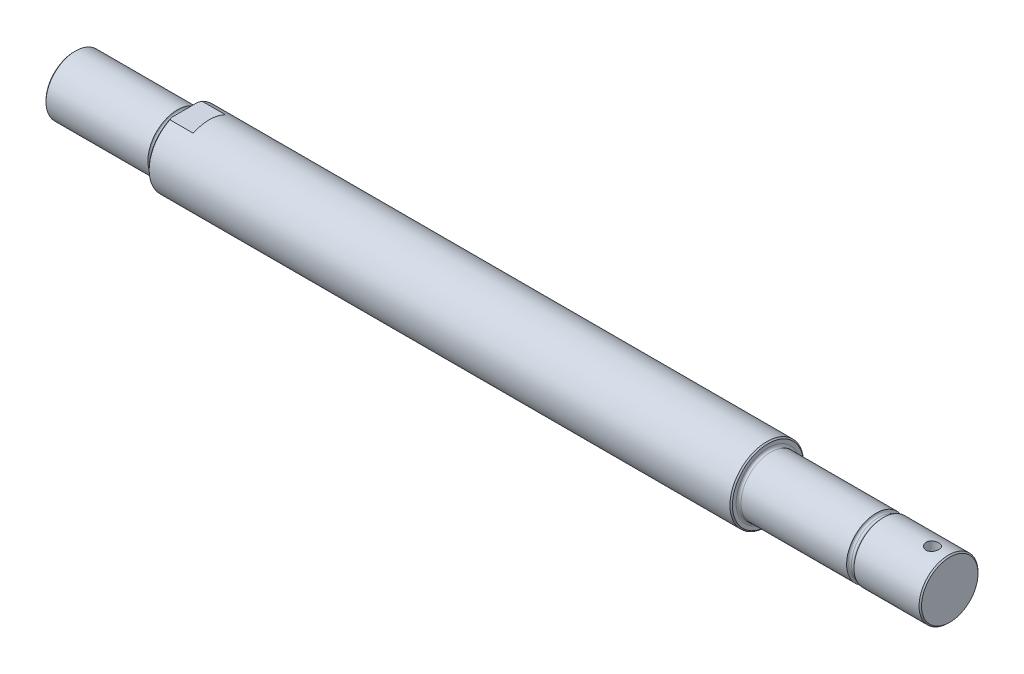
SolidWorks part; units mm, degrees
ref_plane "Front" through (0, 0, 0) normal (0, 0, 1) x (1, 0, 0)
ref_plane "Top" through (0, 0, 0) normal (0, 1, 0) x (1, 0, 0)
ref_plane "Right" through (0, 0, 0) normal (1, 0, 0) x (0, 0, -1)
ref_axis "Axis1" through (-84.4107, 0, 0) along (1, 0, 0)
ref_axis "Axis2" through (0, 64.3378, 0) along (0, -1, 0)
ref_axis "Axis3" through (0, 0, -102.329) along (0, 0, 1)
sketch "Sketch1" plane through (0, 0, 0) normal (0, 0, 1) x (1, 0, 0)
  line L0 (-178.25, 0) -> (178.25, 0) construction
  line L1 (-178.25, 15) -> (178.25, 15)
  line L2 (-178.25, 15) -> (-178.25, 0)
  line L3 (-178.25, 0) -> (178.25, 0)
  line L4 (178.25, 15) -> (178.25, 0)
  point P4 (0, 0)
  dimension "D1" = 15
  dimension "D2" = 356.5
revolve "Revolve1" add sketch "Sketch1" angle 360 about L0
sketch "Sketch2" plane through (0, 0, 0) normal (0, 0, 1) x (1, 0, 0)
  line L0 (178.25, 0) -> (-178.25, 0) construction
  line L1 (178.25, 15) -> (104.25, 15)
  line L2 (178.25, 15) -> (178.25, 12)
  line L3 (178.25, 12) -> (104.25, 12)
  line L4 (104.25, 15) -> (104.25, 12)
  line L5 (-178.25, 15) -> (-133.25, 15)
  line L6 (-178.25, 15) -> (-178.25, 12)
  line L7 (-178.25, 12) -> (-133.25, 12)
  line L8 (-133.25, 15) -> (-133.25, 12)
  line L9 (178.25, -15) -> (178.25, 15) construction
  line L10 (-178.25, 15) -> (-178.25, -15) construction
  line L11 (178.25, 12) -> (151.25, 12)
  line L13 (151.25, 12) -> (148.25, 12)
  line L14 (151.25, 12) -> (151.25, 11)
  line L15 (151.25, 11) -> (148.25, 11)
  line L16 (148.25, 12) -> (148.25, 11)
  line L17 (-133.25, 12) -> (-136.25, 12)
  line L18 (-133.25, 12) -> (-133.25, 11)
  line L19 (-133.25, 11) -> (-136.25, 11)
  line L20 (-136.25, 12) -> (-136.25, 11)
  dimension "D1" = 3
  dimension "D2" = 74
  dimension "D3" = 45
  dimension "D4" = 3
  dimension "D5" = 1
  dimension "D6" = 3
  dimension "D7" = 3
  dimension "D8" = 1
revolve "Cut-Revolve1" cut sketch "Sketch2" angle 360 about L0
sketch "Sketch3" plane through (0, 0, 0) normal (0, 1, 0) x (1, 0, 0)
  line L0 (178.25, 0) -> (171.25, 0)
  line L1 (178.25, -12) -> (178.25, 12) construction
  circle A0 centre (171.25, 0) radius 2.6
  dimension "D2" = 5.2
  dimension "D1" = 7
extrude "Cut-Extrude1" cut sketch "Sketch3" against normal through all both and the other way through all contours A0
sketch "Sketch4" plane through (0, 0, 0) normal (0, 0, 1) x (1, 0, 0)
  line L1 (-133.25, 15) -> (-123.25, 15)
  line L2 (-133.25, 15) -> (-133.25, 13.5)
  line L3 (-133.25, 13.5) -> (-123.25, 13.5)
  line L4 (-123.25, 15) -> (-123.25, 13.5)
  line L5 (-133.25, -15) -> (-123.25, -15)
  line L6 (-133.25, -15) -> (-133.25, -13.5)
  line L7 (-133.25, -13.5) -> (-123.25, -13.5)
  line L8 (-123.25, -15) -> (-123.25, -13.5)
  dimension "D1" = 10
  dimension "D2" = 10
  dimension "D3" = 1.5
  dimension "D4" = 1.5
extrude "Cut-Extrude2" cut sketch "Sketch4" against normal through all both and the other way through all contours L1 L4 L3 L2 | L6 L5 L8 L7
fillet "Fillet1" radius 1 5 edges at (151.25, 11, 0) (148.25, 11, 0) (104.25, 12, 0) (-136.25, 11, 0) (-133.25, 11, 0)
chamfer "Chamfer1" distance 0.5 5 edges at (104.25, 15, 0) (178.25, 12, 0) (-133.25, 0, 15) (-133.25, 0, -15) (-178.25, 12, 0)
cosmetic thread "Cosmetic Thread3" parameters "D1"=41.4999, "D2"=20.704
cosmetic thread "Cosmetic Thread4" parameters "D1"=26.4999, "D2"=20.704
ref_plane "Plane1" through (104.25, 0, 0) normal (1, 0, 0) x (0, 0, -1)
